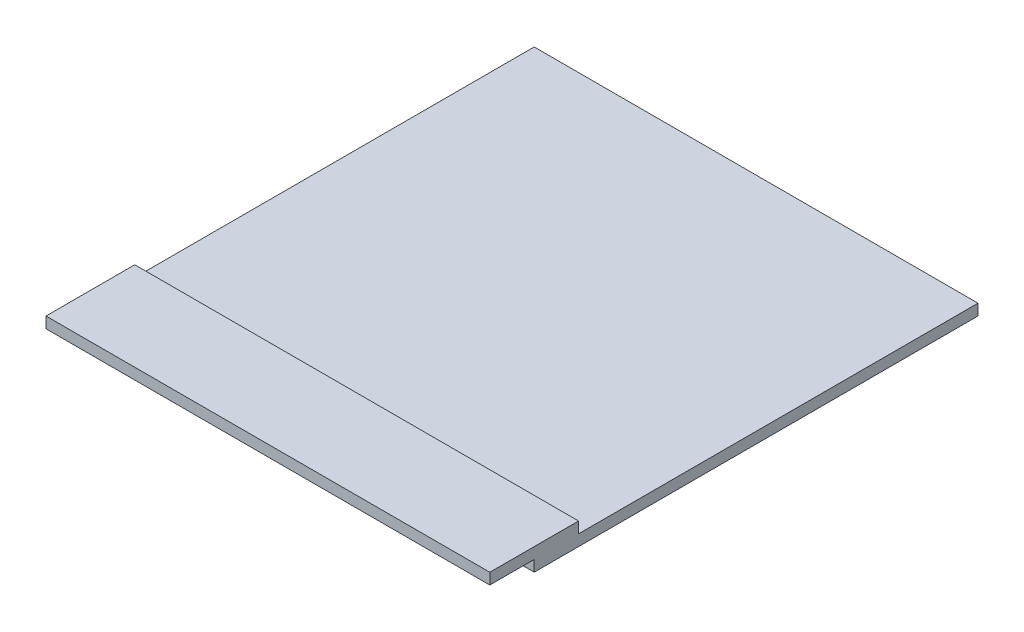
SolidWorks part; units mm, degrees
ref_plane "Front Plane" through (0, 0, 0) normal (0, 0, 1) x (1, 0, 0)
ref_plane "Top Plane" through (0, 0, 0) normal (0, 1, 0) x (1, 0, 0)
ref_plane "Right Plane" through (0, 0, 0) normal (1, 0, 0) x (0, 0, -1)
sketch "Sketch1" plane through (0, 0, 0) normal (0, 1, 0) x (1, 0, 0)
  line L1 (0, 0) -> (200, 0)
  line L2 (0, 0) -> (0, 200)
  line L3 (0, 200) -> (200, 200)
  line L4 (200, 0) -> (200, 200)
  dimension "D1" = 200
  dimension "D2" = 200
extrude "Boss-Extrude1" add sketch "Sketch1" along normal blind 5
sketch "Sketch2" plane through (0, 5, 0) normal (0, 1, 0) x (1, 0, 0)
  line L1 (0, 20) -> (200, 20)
  line L2 (0, 20) -> (0, -20)
  line L3 (0, -20) -> (200, -20)
  line L4 (200, 20) -> (200, -20)
  line L5 (0, 200) -> (0, 0) construction
  line L6 (200, 0) -> (200, 200) construction
  line L7 (0, 0) -> (200, 0) construction
  dimension "D1" = 20
  dimension "D2" = 20
extrude "Boss-Extrude2" add sketch "Sketch2" along normal blind 5
